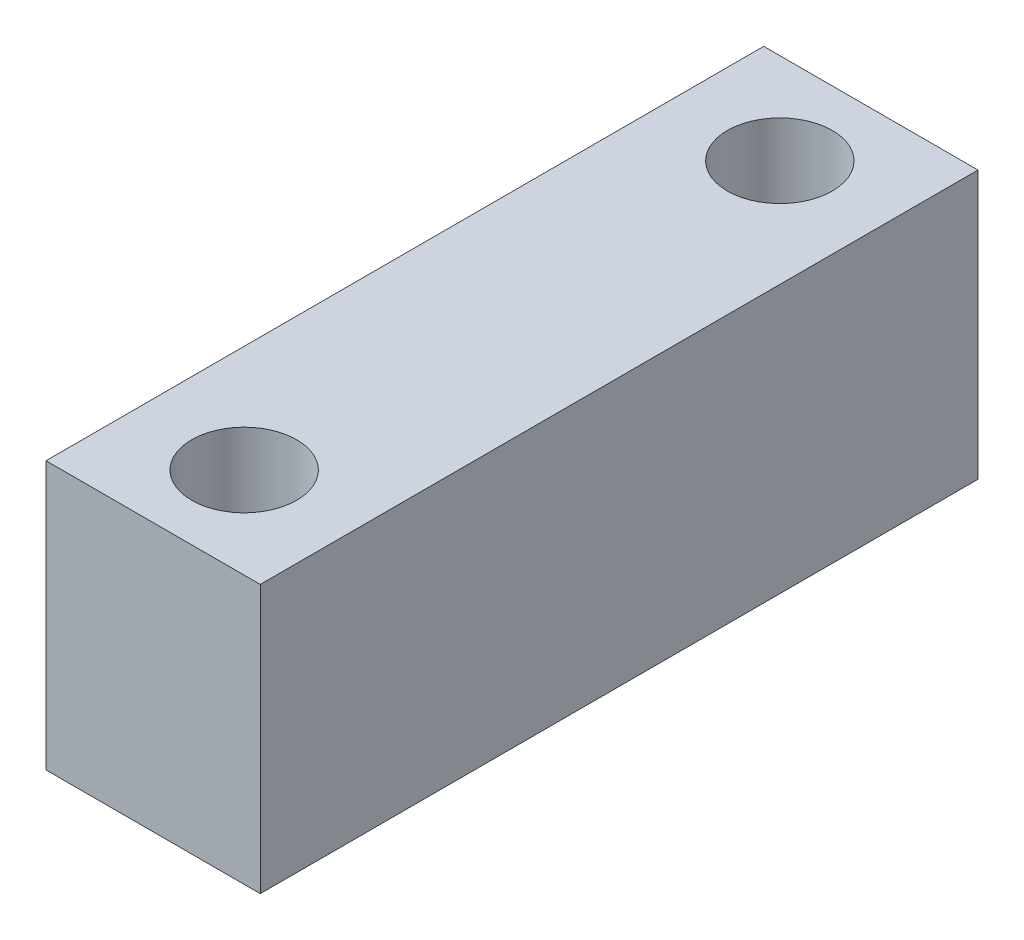
SolidWorks part; units mm, degrees
ref_plane "Front Plane" through (0, 0, 0) normal (0, 0, 1) x (1, 0, 0)
ref_plane "Top Plane" through (0, 0, 0) normal (0, 1, 0) x (1, 0, 0)
ref_plane "Right Plane" through (0, 0, 0) normal (1, 0, 0) x (0, 0, -1)
sketch "Sketch4" plane through (0, 0, 0) normal (0, 1, 0) x (1, 0, 0)
  line L0 (-66.4138, 23.2509) -> (-56.2538, 23.2509)
  line L1 (-56.2538, 23.2509) -> (-56.2538, -10.7851)
  line L2 (-56.2538, -10.7851) -> (-66.4138, -10.7851)
  line L3 (-66.4138, -10.7851) -> (-66.4138, 23.2509)
extrude "Boss-Extrude1" add sketch "Sketch4" along normal blind 12.7
sketch "Sketch5" plane through (0, 12.7, 0) normal (0, 1, 0) x (1, 0, 0)
  line L0 (-66.4138, 6.2329) -> (-56.2538, 6.2329) construction
  line L1 (-66.4138, 23.2509) -> (-66.4138, -10.7851) construction
  line L2 (-56.2538, -10.7851) -> (-56.2538, 23.2509) construction
  line L3 (-61.3338, 18.9329) -> (-61.3338, -6.4671) construction
  point P9 (-61.3338, 6.2329)
hole_wizard "#10 Clearance Hole1" positions "Sketch6" profile "Sketch7" hole size "#10" standard "ANSI Inch" end condition through all
sketch "Sketch6" plane through (0, 12.7, 0) normal (0, 1, 0) x (1, 0, 0)
  point P0 (-61.3338, 18.9329)
  point P3 (-61.3338, -6.4671)
sketch "Sketch7" plane through (-61.3338, 12.7, -18.9329) normal (1, 0, 0) x (0, 0, 1)
  line L0 (0, 0) -> (0, 12.7)
  line L1 (0, 12.7) -> (2.4892, 12.7)
  line L2 (2.4892, 12.7) -> (2.4892, 0)
  line L5 (2.4892, 0) -> (0, 0)
  line L11 (0, -6.35) -> (0, 107.95) construction
  dimension "Thru Hole Dia." = 4.9784
  dimension "Thru Hole Depth" = 12.7
